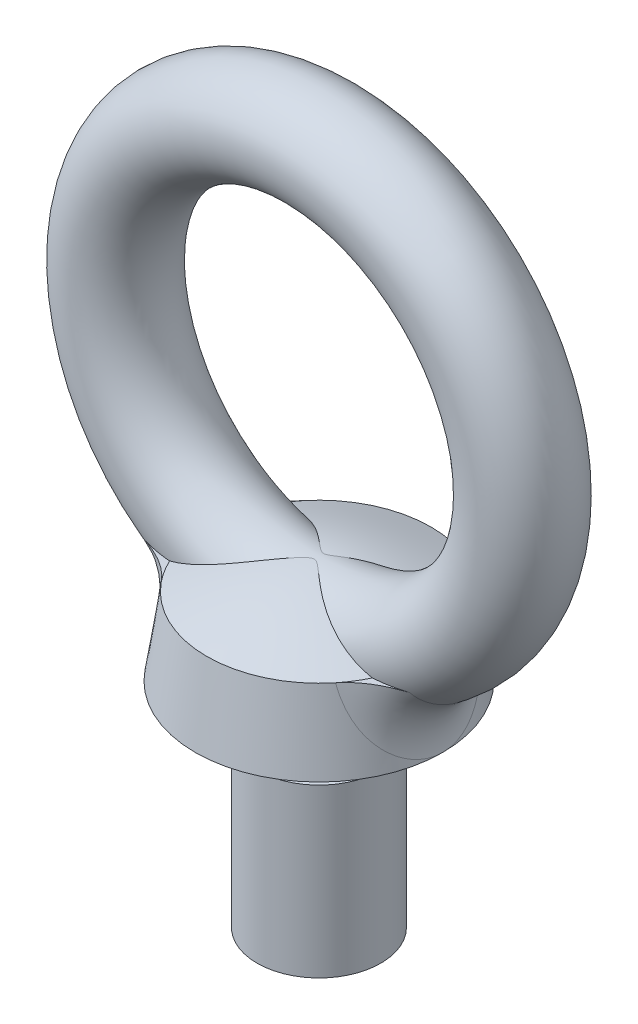
SolidWorks part; units mm, degrees
ref_plane "Front Plane" through (0, 0, 0) normal (0, 0, 1) x (1, 0, 0)
ref_plane "Top Plane" through (0, 0, 0) normal (0, 1, 0) x (1, 0, 0)
ref_plane "Right Plane" through (0, 0, 0) normal (1, 0, 0) x (0, 0, -1)
sketch "Sketch1" plane through (0, 0, 0) normal (0, 0, 1) x (1, 0, 0)
  line L0 (0, 0) -> (0, -80.1248) construction
  line L1 (0, -12) -> (7.249, -12)
  line L2 (7.249, -12) -> (8, -17)
  line L3 (8, -17) -> (4, -17)
  line L4 (4, -20) -> (4, -30.8)
  line L5 (0, -12) -> (0, -32)
  line L6 (3, -19) -> (3, -18)
  line L7 (4, -20) -> (-10.8447, -20) construction
  circle A0 centre (0, 0) radius 16.3 construction
  arc A1 (3, -19) -> (4, -20) centre (4, -19) ccw
  arc A2 (9.5998, -13.1732) -> (8, -17) centre (11.9556, -16.4059) ccw construction
  arc A3 (4, -17) -> (3, -18) centre (4, -18) ccw
  arc A4 (0, -32) -> (4, -30.8) centre (0, -24.7333) ccw
  point P21 (3, -20)
  dimension "D2" = 16
revolve "Revolve1" add sketch "Sketch1" angle 360 about L0
cosmetic thread "ThreadCosmetic1" parameters "dp"=6.619
sketch "Sketch2" plane through (0, 0, 0) normal (0, 0, 1) x (1, 0, 0)
  circle A0 centre (0, 0) radius 16.3 construction
  circle A1 centre (0, 0) radius 16.3 construction
  circle A2 centre (0, 0) radius 10
  dimension "b" = 20
sketch "Sketch3" plane through (0, 0, 0) normal (0, 1, 0) x (1, 0, 0)
  circle A0 centre (-13.15, 0) radius 3.15
  point P2 (-16.3, 0)
  point P3 (-10, 0)
sweep "Sweep1" add profiles "Sketch3" path "Sketch2"
fillet "Fillet2" radius 4 2 edges at (7.6009, -14.397, -0.3517) (-7.6009, -14.397, 0.3517)
sketch "Sketch4" plane through (0, 0, 0) normal (1, 0, 0) x (0, 0, -1)
  line L0 (0, -10.01) -> (-5.2122, -10.01) construction
  line L9 (0, -7.267) -> (0, -17.3967) construction
  line L10 (7.249, -12) -> (0, -12)
  line L11 (0, -10.01) -> (0, -12)
  spline S0 degree 3 poles (0, -10.01) (2.4461, -10.01) (4.8476, -11.005) (7.249, -12) knots 0 0 0 0 1 1 1 1
  point P5 (0, -10)
  dimension "D1" = 0.01
revolve "Revolve2" add sketch "Sketch4" angle 360 about L9
sketch "Sketch5" plane through (0, 0, 0) normal (0, 0, 1) x (1, 0, 0)
  line L0 (-4.6905, -19.6548) -> (-4, -19.6548)
  line L1 (-4, -19.6548) -> (-3.402, -20)
  line L2 (-3.402, -20) -> (-4, -20.3453)
  line L3 (-4, -20.3453) -> (-4.6905, -20.3453)
  line L4 (-4.6905, -20.3453) -> (-4.6905, -19.6548)
  line L5 (4, -20) -> (-4, -20) construction
  line L6 (-4, -20) -> (-4, -30.8) construction
  line L7 (0, -18.4833) -> (0, -25.3769) construction
  dimension "D1" = 0.6905
revolve "Cut-Revolve10" [suppressed] cut sketch "Sketch5" angle 360 about L7
pattern_linear "LPattern10" [suppressed] count 14 spacing 0.8286 along (0, -1, 0) of bodies 109
equation "\"D1@Sketch5\"= ( \"d@Sketch1\"-\"dp@ThreadCosmetic1\" )  / 2"
equation "\"D3@LPattern10\"=\"D1@Sketch5\" * 1.2"
equation "\"D1@LPattern10\" = (  \"l@Sketch1\" - \"e@Sketch1\" )  / \"D3@LPattern10\""
